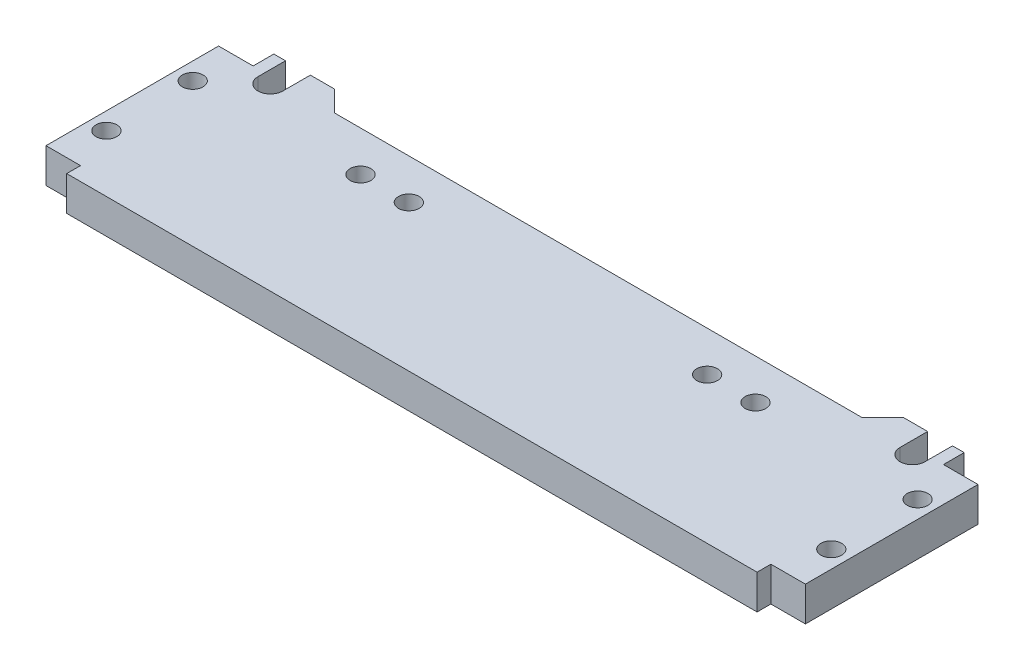
SolidWorks part; units mm, degrees
ref_plane "Front Plane" through (0, 0, 0) normal (0, 0, 1) x (1, 0, 0)
ref_plane "Top Plane" through (0, 0, 0) normal (0, 1, 0) x (1, 0, 0)
ref_plane "Right Plane" through (0, 0, 0) normal (1, 0, 0) x (0, 0, -1)
sketch "Sketch1" plane through (0, 0, 0) normal (1, 0, 0) x (0, 0, -1)
  line L1 (-17.1369, 5.602) -> (9.8631, 5.602)
  line L2 (-17.1369, 5.602) -> (-17.1369, 0.602)
  line L3 (-17.1369, 0.602) -> (9.8631, 0.602)
  line L4 (9.8631, 5.602) -> (9.8631, 0.602)
  dimension "D1" = 27
  dimension "D2" = 5
extrude "Boss-Extrude1" add sketch "Sketch1" along normal blind 110
sketch "Sketch2" plane through (0, 0.602, 0) normal (0, -1, 0) x (1, 0, 0)
  line L1 (0, -9.8631) -> (5, -9.8631)
  line L2 (0, -9.8631) -> (0, -7.3631)
  line L3 (0, -7.3631) -> (5, -7.3631)
  line L4 (5, -9.8631) -> (5, -7.3631)
  dimension "D1" = 5
  dimension "D2" = 2.5
sketch "Sketch5" plane through (0, 0, 0) normal (-1, 0, 0) x (0, 0, 1)
  line L0 (0, 0.602) -> (0, 5.602) construction
  line L1 (17.1369, 0.602) -> (-9.8631, 0.602) construction
  line L2 (-9.8631, 5.602) -> (17.1369, 5.602) construction
sketch "Sketch6" plane through (0, 5.602, 0) normal (0, 1, 0) x (1, 0, 0)
  line L1 (0, -17.1369) -> (5, -17.1369)
  line L2 (0, -17.1369) -> (0, -15.1369)
  line L3 (0, -15.1369) -> (5, -15.1369)
  line L4 (5, -17.1369) -> (5, -15.1369)
  dimension "D1" = 5
  dimension "D2" = 2
sketch "Sketch7" plane through (0, 5.602, 0) normal (0, 1, 0) x (1, 0, 0)
  line L0 (110, -3.6369) -> (0, 0) construction
  line L1 (110, 9.8631) -> (110, -17.1369) construction
  line L2 (55, -1.8184) -> (55, -17.1369) construction
  line L3 (110, -17.1369) -> (0, -17.1369) construction
sketch "Sketch8" plane through (0, 0, 17.1369) normal (0, 0, 1) x (1, 0, 0)
  line L0 (55, 5.602) -> (55, 0.602) construction
  line L1 (110, 0.602) -> (0, 0.602) construction
ref_plane "Plane3" through (55, 0, 0) normal (1, 0, 0) x (0, 0, -1)
sketch "Sketch13" plane through (0, 5.602, 0) normal (0, 1, 0) x (1, 0, 0)
  line L0 (55, -1.8184) -> (4.7941, -1.8184) construction
  line L1 (29.897, -1.8184) -> (29.897, 9.8631) construction
  line L2 (110, 9.8631) -> (0, 9.8631) construction
  line L3 (29.897, 4.0223) -> (26.397, 4.0223) construction
  line L4 (17.3455, 4.0223) -> (17.3455, 9.8631) construction
  line L5 (29.897, 4.0223) -> (33.397, 4.0223) construction
  dimension "D1" = 3.5
  dimension "D2" = 3.5
hole_wizard "M3 Tapped Hole1" positions "3DSketch2" profile "Sketch14" tap size "M3" standard "ISO"
sketch3d "3DSketch2"
  point P0 (26.397, 5.602, -4.0223)
  point P3 (33.397, 5.602, -4.0223)
sketch "Sketch14" plane through (26.397, 5.602, -4.0223) normal (1, 0, 0) x (0, 0, 1)
  line L0 (0, 0) -> (0, 8.2511)
  line L1 (0, 8.2511) -> (1.25, 7.5)
  line L2 (1.25, 7.5) -> (1.25, 6)
  line L3 (1.25, 6) -> (1.5, 6)
  line L4 (1.5, 6) -> (1.5, 0)
  line L5 (1.5, 0) -> (0, 0)
  line L10 (0, 8.2511) -> (-1.25, 7.5) construction
  line L11 (0, -6.35) -> (0, 107.95) construction
  dimension "Tap Drill Dia." = 2.5
  dimension "Tap Drill Depth" = 7.5
  dimension "Thread Major Dia." = 3
  dimension "Thread Depth" = 6
  dimension "Drill Angle" = 118
ref_plane "Plane4" through (55, 0, 0) normal (1, 0, 0) x (0, 0, -1)
mirror "Mirror3" about plane through (55, 0, 0) normal (1, 0, 0) of "M3 Tapped Hole1"
extrude "Cut-Extrude1" cut sketch "Sketch6" against normal blind 10 contours L4 L3 L2 L1
mirror "Mirror4" about plane through (55, 0, 0) normal (1, 0, 0) of "Cut-Extrude1"
sketch "Sketch17" plane through (0, 5.602, 0) normal (0, 1, 0) x (1, 0, 0)
  line L0 (110, 9.8631) -> (105, 9.8631) construction
  line L1 (110, 9.8631) -> (0, 9.8631) construction
  line L2 (105, 9.8631) -> (105, 12.8631)
  line L3 (103.25, 12.8631) -> (99.674, 12.8631)
  line L4 (105, 12.8631) -> (103.25, 12.8631)
  line L5 (105, 9.8631) -> (97.924, 9.8631)
  line L6 (99.674, 12.8631) -> (93.2002, 12.8631)
  line L13 (93.2002, 12.8631) -> (93.2002, 9.8631)
  line L14 (93.2002, 9.8631) -> (97.924, 9.8631)
  dimension "D4" = 3
  dimension "D1" = 5
  dimension "D2" = 3
  dimension "D3" = 1.75
extrude "Boss-Extrude2" add sketch "Sketch17" against normal blind 5
sketch "Sketch18" plane through (0, 5.602, 0) normal (0, 1, 0) x (1, 0, 0)
  line L0 (55, -17.1369) -> (55, 9.8631) construction
  line L1 (93.2002, 9.8631) -> (0, 9.8631) construction
sketch "Sketch19" plane through (0, 0, -9.8631) normal (0, 0, -1) x (-1, 0, 0)
  line L0 (-55, 5.602) -> (-55, 0.602) construction
  line L1 (-93.2002, 0.602) -> (0, 0.602) construction
ref_plane "Plane5" through (55, 0, 0) normal (-1, 0, 0) x (0, 0, 1)
sketch "Sketch20" plane through (0, 5.602, 0) normal (0, 1, 0) x (1, 0, 0)
  line L0 (97.924, 9.8631) -> (97.924, 5.623) construction
sketch "Sketch21" plane through (0, 5.602, 0) normal (0, 1, 0) x (1, 0, 0)
  line L0 (96.5031, 12.8631) -> (98.3031, 12.8631)
  line L1 (105, 12.8631) -> (93.2002, 12.8631) construction
  line L2 (96.5031, 12.8631) -> (94.7026, 12.8631)
  line L3 (96.5031, 12.8631) -> (96.5031, 9.2179) construction
  line L4 (98.3031, 12.8631) -> (98.3031, 7.8631)
  line L5 (94.7026, 12.8631) -> (94.7026, 7.8631)
  arc A0 (98.3031, 7.8631) -> (94.7026, 7.8631) centre (96.5028, 7.8631) cw
  dimension "D1" = 5
  dimension "D2" = 1.8
sketch "Sketch22" plane through (0, 5.602, 0) normal (0, 1, 0) x (1, 0, 0)
  line L0 (101.5051, 12.8631) -> (101.5051, 11.6291) construction
  line L1 (105, 12.8631) -> (93.2002, 12.8631) construction
  line L2 (101.5051, 12.8631) -> (103.3051, 12.8631)
  line L3 (99.7051, 12.8631) -> (99.7051, 8.8631)
  line L4 (101.5051, 12.8631) -> (99.7051, 12.8631)
  line L6 (103.3051, 8.8631) -> (103.3051, 12.8631)
  arc A1 (103.3051, 8.8631) -> (99.7051, 8.8631) centre (101.5051, 8.8631) cw
  dimension "D1" = 1.8
  dimension "D2" = 1.8
  dimension "D3" = 4
extrude "Cut-Extrude3" cut sketch "Sketch22" against normal blind 10 contours L4 L3 A1 L6 L2
ref_plane "Plane6" through (55, 0, 0) normal (-1, 0, 0) x (0, 0, 1)
chamfer "Chamfer1" distance 3 angle 45 1 edges at (93.2002, 3.102, -12.8631)
mirror "Mirror8" about plane through (55, 0, 0) normal (-1, 0, 0) of "Cut-Extrude3", "Boss-Extrude2", "Chamfer1"
sketch "Sketch23" plane through (0, 0.602, 0) normal (0, -1, 0) x (-1, 0, 0)
  line L0 (-107.5, -2.6369) -> (-107.5, 9.8631) construction
  line L3 (-107.5, -2.6369) -> (-110, -2.6369) construction
  line L4 (-110, -15.1369) -> (-110, 9.8631) construction
  line L5 (-110, 9.8631) -> (-105, 9.8631) construction
  line L6 (-107.5, 3.6131) -> (-110, 3.6131) construction
hole_wizard "Ø3.0mm Dowel Hole1" positions "Sketch25" profile "Sketch24" hole size "Ø3.0" standard "ISO"
sketch "Sketch25" plane through (0, 0.602, 0) normal (0, -1, 0) x (-1, 0, 0)
  line L0 (-110, -15.1369) -> (-105, -15.1369) construction
  point P0 (-107.5, 3.6131)
  point P3 (-107.5, -8.8869)
  dimension "D1" = 6.25
sketch "Sketch24" plane through (107.5, 0.602, -3.6131) normal (1, 0, 0) x (0, 0, -1)
  line L0 (0, 0) -> (0, 20.9013)
  line L1 (0, 20.9013) -> (1.5, 20)
  line L2 (1.5, 20) -> (1.5, 0)
  line L5 (1.5, 0) -> (0, 0)
  line L10 (0, 20.9013) -> (-1.5, 20) construction
  line L11 (0, -6.35) -> (0, 107.95) construction
  dimension "Hole Dia." = 3
  dimension "Hole Depth" = 20
  dimension "Drill Angle" = 118
mirror "Mirror9" about plane through (55, 0, 0) normal (-1, 0, 0) of "Ø3.0mm Dowel Hole1"
